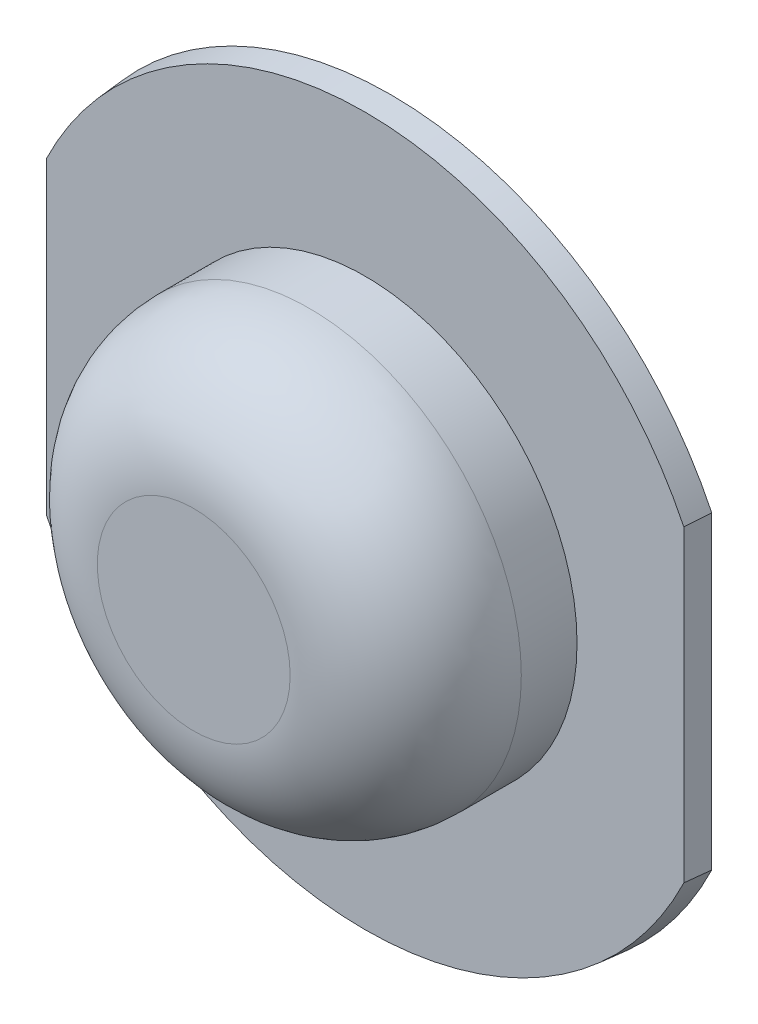
SolidWorks part; units mm, degrees
material "Silicon"
ref_plane "Front Plane" through (0, 0, 0) normal (0, 0, 1) x (1, 0, 0)
ref_plane "Top Plane" through (0, 0, 0) normal (0, 1, 0) x (1, 0, 0)
ref_plane "Right Plane" through (0, 0, 0) normal (1, 0, 0) x (0, 0, -1)
ref_axis "Axis1" through (0, 0, 0) along (0, 0, 1)
sketch "Sketch1" plane through (0, 0, 0) normal (0, 0, 1) x (1, 0, 0)
  line L0 (50, 24.0884) -> (50, -24.0884)
  line L1 (-50, 24.0884) -> (-50, -24.0884)
  arc A0 (-50, -24.0884) -> (50, -24.0884) centre (0, 0) ccw
  arc A1 (50, 24.0884) -> (-50, 24.0884) centre (0, 0) ccw
  dimension "D1" = 55.5
  dimension "D2" = 100
extrude "Boss-Extrude1" add sketch "Sketch1" along normal blind 4 draft 5
sketch "Sketch5" plane through (0, 0, 0) normal (0, 0, 1) x (1, 0, 0)
  line L0 (0, 0) -> (0, -41.75) construction
  line L1 (43.25, 43.25) -> (-43.25, 43.25) construction
  line L2 (43.25, 43.25) -> (43.25, -43.25) construction
  line L3 (43.25, -43.25) -> (-43.25, -43.25) construction
  line L4 (-43.25, 43.25) -> (-43.25, -43.25) construction
  line L5 (43.25, 43.25) -> (-43.25, -43.25) construction
  line L6 (43.25, -43.25) -> (-43.25, 43.25) construction
  line L7 (0, 0) -> (0, 41.75) construction
  line L8 (0, 0) -> (-41.75, 0) construction
  line L9 (0, 0) -> (41.75, 0) construction
  line L11 (-36, 36) -> (36, 36) construction
  line L12 (-36, 36) -> (-36, -36) construction
  line L13 (-36, -36) -> (36, -36) construction
  line L14 (36, 36) -> (36, -36) construction
  line L15 (-36, 36) -> (36, -36) construction
  line L16 (-36, -36) -> (36, 36) construction
  circle A0 centre (18.497, -18.497) radius 24.753 construction
  circle A1 centre (-18.497, -18.497) radius 24.753 construction
  circle A2 centre (18.497, 18.497) radius 24.753 construction
  circle A3 centre (-18.497, 18.497) radius 24.753 construction
  spline S0 degree 3 poles (45.3558, 18.4579) (39.9657, 0) (45.3558, -18.4579) (38.0677, -38.0677) (18.4579, -45.3558) (0, -39.9657) (-18.4579, -45.3558) (-38.0677, -38.0677) (-45.3558, -18.4579) (-39.9657, 0) (-45.3558, 18.4579) (-38.0677, 38.0677) (-18.4579, 45.3558) (0, 39.9657) (18.4579, 45.3558) (38.0677, 38.0677) (45.3558, 18.4579) (39.9657, 0) (45.3558, -18.4579) knots -0.188146 -0.125 -0.061854 0 0.061854 0.125 0.188146 0.25 0.311854 0.375 0.438146 0.5 0.561854 0.625 0.688146 0.75 0.811854 0.875 0.938146 1 1.061854 1.125 1.188146 only from (41.75, 0) to (41.75, 0)
  point P0 (0, 0)
  dimension "D1" = 86.5
  dimension "D2" = 83.5
  dimension "D3" = 72
extrude "Boss-Extrude2" [suppressed] add sketch "Sketch5" along normal blind 29.78 draft 4
fillet "Fillet1" [suppressed] radius 12
sketch "Sketch6" plane through (0, 0, 0) normal (0, 0, -1) x (-1, 0, 0)
  line L1 (-26.27, -26.27) -> (26.27, -26.27)
  line L2 (-26.27, -26.27) -> (-26.27, 26.27)
  line L3 (-26.27, 26.27) -> (26.27, 26.27)
  line L4 (26.27, -26.27) -> (26.27, 26.27)
  line L5 (-26.27, -26.27) -> (26.27, 26.27) construction
  line L6 (-26.27, 26.27) -> (26.27, -26.27) construction
  point P0 (0, 0)
  dimension "D1" = 52.54
extrude "Cut-Extrude2" cut sketch "Sketch6" against normal blind 2.35
sketch "Sketch7" plane through (0, 0, 0) normal (0, 1, 0) x (1, 0, 0)
  line L0 (0, -2.35) -> (0, -27.35)
  line L1 (26.27, -2.35) -> (-26.27, -2.35) construction
  line L2 (0, -2.35) -> (25, -2.35)
  arc A0 (0, -27.35) -> (25, -2.35) centre (0, -2.35) ccw
  dimension "D1" = 25
revolve "Cut-Revolve1" cut sketch "Sketch7" angle 360 about L0
sketch "Sketch8" plane through (0, 0, 2.35) normal (0, 0, -1) x (-1, 0, 0)
  line L0 (19.5512, 19.5512) -> (-19.5512, -19.5512) construction
  line L1 (-26.27, 26.27) -> (-26.27, -26.27) construction
  line L3 (-19.887, -15.1494) -> (-15.1494, -19.887)
  line L4 (-19.887, -15.1494) -> (-22.5387, -17.8011)
  line L5 (-22.5387, -20.6295) -> (-20.6295, -22.5387)
  line L6 (-15.1494, -19.887) -> (-17.8011, -22.5387)
  line L7 (-19.887, -15.1494) -> (-19.2153, -23.9529) construction
  line L8 (-23.9529, -19.2153) -> (-15.1494, -19.887) construction
  circle A0 centre (0, 0) radius 25 construction
  arc A1 (-22.5387, -17.8011) -> (-22.5387, -20.6295) centre (-21.1245, -19.2153) ccw
  arc A2 (-20.6295, -22.5387) -> (-17.8011, -22.5387) centre (-19.2153, -21.1245) ccw
  point P4 (0, 0)
  point P45 (0, 0)
  dimension "D4" = 2
  dimension "D1" = 45
  dimension "D2" = 5.75
  dimension "D3" = 6.7
extrude "Cut-Extrude3" cut sketch "Sketch8" against normal blind 0.8
pattern_circular "CirPattern1" count 4 over 360 about axis through (0, 0, 0) along (0, 0, 1) of "Cut-Extrude3"
sketch "Sketch9" plane through (0, 0, 4) normal (0, 0, 1) x (1, 0, 0)
  circle A0 centre (0, 0) radius 33.02
  dimension "D1" = 66.04
extrude "Boss-Extrude3" add sketch "Sketch9" along normal blind 26.68
fillet "Fillet2" radius 18 1 edges at (33.02, 0, 30.68)
sketch "Sketch10" plane through (0, 0, 0) normal (0, 0, -1) x (-1, 0, 0)
  line L0 (50, -24.0884) -> (-50, 24.0884) construction
  point P4 (0, 0)
